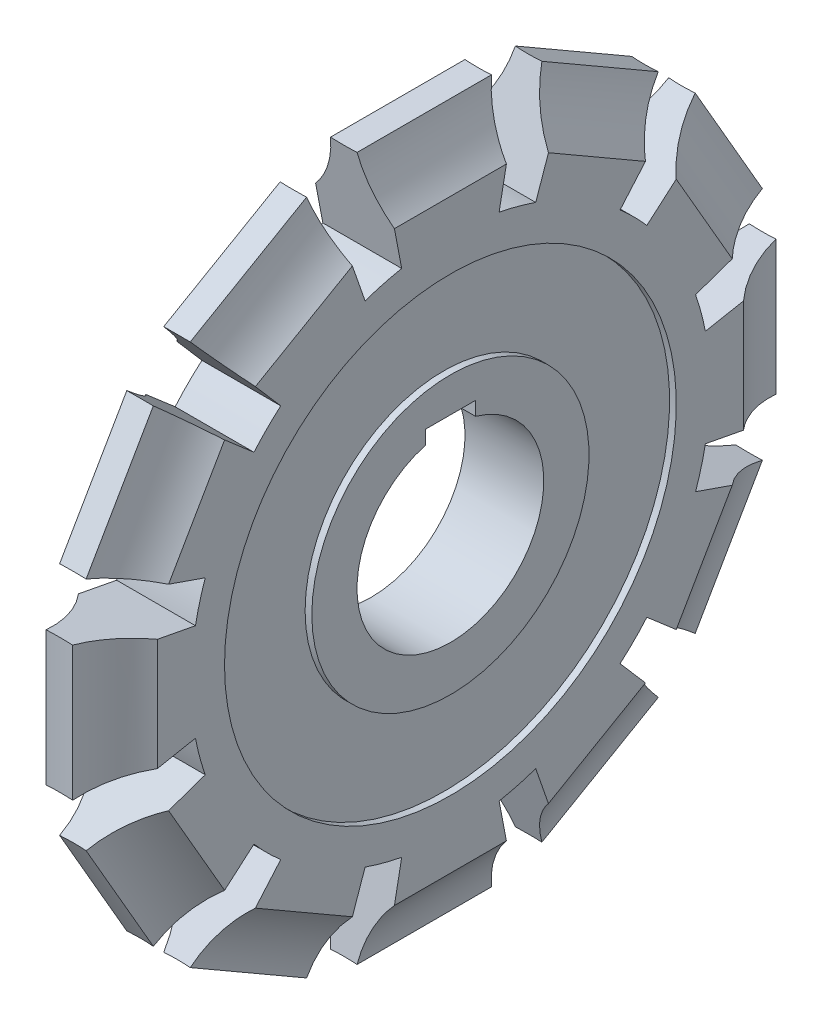
SolidWorks part; units mm, degrees
ref_plane "前视基准面" through (0, 0, 0) normal (0, 0, 1) x (1, 0, 0)
ref_plane "上视基准面" through (0, 0, 0) normal (0, 1, 0) x (1, 0, 0)
ref_plane "右视基准面" through (0, 0, 0) normal (1, 0, 0) x (0, 0, -1)
sketch "Sketch1" plane through (0, 0, 0) normal (0, 0, 1) x (1, 0, 0)
  line L0 (-2.9329, 21.812) -> (-2.9329, -21.812)
  line L1 (0, -43.6413) -> (-1.6864, -23.7125) construction
  line L2 (0, -43.6413) -> (-6.2409, -4.238) construction
  line L3 (-1.6864, -23.7125) -> (-3.1204, -23.9396) construction
  line L4 (2.9329, -21.812) -> (2.9329, 21.812)
  line L5 (2.9329, 0) -> (-2.9329, 0)
  line L6 (-1000, 0) -> (49000, 0) construction
  arc A0 (0.9862, -26.1701) -> (-0.9862, -26.1701) centre (0, -43.6413) ccw
  arc A1 (2.9329, -21.812) -> (-2.9329, -21.812) centre (0, -43.6413) ccw construction
  circle A2 centre (0, -43.6413) radius 20 construction
  circle A3 centre (0, -43.6413) radius 18.7939 construction
  arc A4 (-0.9862, -26.1701) -> (-2.9329, -21.812) centre (-8.9313, -27.1052) ccw
  arc A5 (2.9329, -21.812) -> (0.9862, -26.1701) centre (8.9313, -27.1052) ccw
  arc A6 (0.9862, 26.1701) -> (-0.9862, 26.1701) centre (0, 43.6413) cw
  arc A7 (-0.9862, 26.1701) -> (-2.9329, 21.812) centre (-8.9313, 27.1052) cw
  arc A8 (2.9329, 21.812) -> (0.9862, 26.1701) centre (8.9313, 27.1052) cw
sketch "Sketch2" plane through (0, 0, 0) normal (0, 1, 0) x (1, 0, 0)
  line L0 (0, -1000) -> (0, 49000) construction
extrude "Boss-Extrude1" add sketch "Sketch1" along normal blind 5 and the other way blind 5 contours A5 L4 L5 L0 A4 A0 | L4 A8 A6 A7 L0 L5 region at (0, 12.2128, 0) region at (0, -12.2128, 0)
sketch "Sketch3" plane through (0, 0, 0) normal (0, 0, 1) x (1, 0, 0)
  line L0 (-1000, 0) -> (49000, 0) construction
pattern_circular "CirPattern1" count 12 over 360 about axis through (-1000, 0, 0) along (1, 0, 0) of "Boss-Extrude1"
sketch "Sketch4" plane through (-2.9329, 0, 0) normal (-1, 0, 0) x (0, 0, 1)
  circle A0 centre (0, 0) radius 16.812
  circle A1 centre (0, 0) radius 10.3146
extrude "Cut-Extrude1" cut sketch "Sketch4" against normal blind 0.5
sketch "Sketch5" plane through (-2.9329, 0, 0) normal (-1, 0, 0) x (0, 0, 1)
  circle A0 centre (0, 0) radius 6.9507
extrude "Cut-Extrude2" cut sketch "Sketch5" against normal blind 46.5
sketch "Sketch6" plane through (-2.9329, 0, 0) normal (-1, 0, 0) x (0, 0, 1)
  line L0 (-26.1701, -5) -> (-18.9753, -3.6254)
  line L1 (-26.1701, 5) -> (-18.9753, 3.6254)
  line L2 (-26.1701, -5) -> (-18.6603, -5)
  line L3 (-18.6603, -5) -> (-21.3897, -6.5759) construction
  line L4 (-26.1701, 5) -> (-18.6603, 5)
  arc A0 (-18.6603, 5) -> (-18.9753, 3.6254) centre (0, 0) ccw
  arc A1 (-18.9753, -3.6254) -> (-18.6603, -5) centre (0, 0) ccw
extrude "Cut-Extrude3" cut sketch "Sketch6" against normal blind 46.5
pattern_circular "CirPattern2" count 12 over 360 about axis through (-1000, 0, 0) along (1, 0, 0) of "Cut-Extrude3"
ref_plane "Plane1" through (0, 18.9753, 0) normal (0, 1, 0) x (1, 0, 0)
sketch "Sketch10" plane through (-2.4329, 0, 0) normal (-1, 0, 0) x (0, 0, 1)
  line L1 (-1.8722, 6.174) -> (1.8722, 6.174)
  line L2 (-1.8722, 6.174) -> (-1.8722, 7.7275)
  line L3 (-1.8722, 7.7275) -> (1.8722, 7.7275)
  line L4 (1.8722, 6.174) -> (1.8722, 7.7275)
  line L5 (-1.8722, 6.174) -> (1.8722, 7.7275) construction
  line L6 (-1.8722, 7.7275) -> (1.8722, 6.174) construction
  circle A0 centre (0, 0) radius 6.9507 construction
  point P0 (0, 6.9507)
extrude "Cut-Extrude4" cut sketch "Sketch10" against normal blind 46.5 and the other way blind 46.5
mirror "Mirror3" about plane through (0, 0, 0) normal (1, 0, 0) of "Cut-Extrude2", "Cut-Extrude1"
